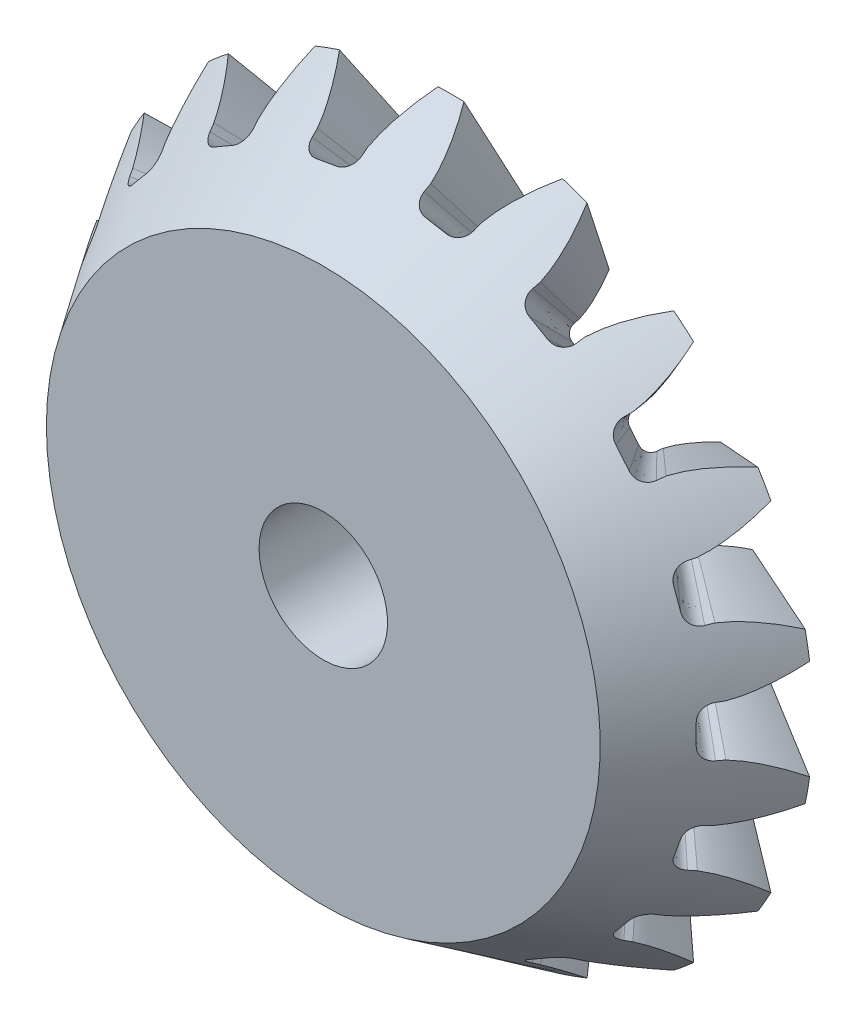
SolidWorks part; units mm, degrees
ref_plane "Front Plane" through (0, 0, 0) normal (0, 0, 1) x (1, 0, 0)
ref_plane "Top Plane" through (0, 0, 0) normal (0, 1, 0) x (1, 0, 0)
ref_plane "Right Plane" through (0, 0, 0) normal (1, 0, 0) x (0, 0, -1)
ref_axis "Gear Axis" through (0, 0, -1.3521) along (0, 0, 1)
sketch "Blank Sketch" plane through (0, 0, 0) normal (0, 1, 0) x (1, 0, 0)
  line L0 (0, 0) -> (0, -27.0416) construction
  line L1 (0, 0) -> (22.5, -15) construction
  line L2 (0, 0) -> (15.0115, -10.0077) construction
  line L3 (11.176, -15.7611) -> (15.6135, -9.1047)
  line L4 (15.6135, -9.1047) -> (23.5324, -13.4515)
  line L5 (23.5324, -13.4515) -> (17.9981, -21.7528)
  line L6 (17.9981, -21.7528) -> (4.175, -21.7528)
  line L7 (4.175, -21.7528) -> (4.175, -15.7611)
  line L8 (4.175, -15.7611) -> (11.176, -15.7611)
  line L9 (22.5, -15) -> (23.5324, -13.4515) construction
  line L10 (22.5, -15) -> (17.9981, -21.7528) construction
  line L11 (15.0115, -10.0077) -> (11.176, -15.7611) construction
  dimension "Axis" = 27.0416
  dimension "Cone" = 56.31
  dimension "Heel" = 27.0416
  dimension "Toe Cone" = 56.31
  dimension "Toe" = 18.0416
  dimension "Heel Square" = 90
  dimension "Addendum" = 1.8611
  dimension "Root Square" = 90
  dimension "Heel Rim" = 8.1158
  dimension "Toe Square" = 90
  dimension "Toe Rim" = 6.9147
  dimension "Front Square" = 90
  dimension "Face" = 4.927
  dimension "Back" = 13.8231
  dimension "Front" = 7.001
revolve "Blank" add sketch "Blank Sketch" angle 360 about L0
sketch "Cone Sketch" plane through (0, 0, 0) normal (0, 1, 0) x (1, 0, 0)
  line L0 (0, 0) -> (0, -27.0416) construction
  line L1 (0, 0) -> (24.5801, -16.3868)
  line L2 (0, 0) -> (12.9314, -8.6209)
  dimension "Axis" = 27.0416
  dimension "Toe Cone" = 56.31
  dimension "Heel Cone" = 56.31
  dimension "Heel" = 29.5416
  dimension "Toe" = 15.5416
ref_plane "Heel Plane" through (24.5801, 0, 16.3868) normal (0.8321, 0, 0.5547) x (0.5547, 0, -0.8321)
ref_plane "Toe Plane" through (12.9314, 0, 8.6209) normal (0.8321, 0, 0.5547) x (0.5547, 0, -0.8321)
sketch "Heel Section Sketch" plane through (24.5801, 0, 16.3868) normal (0.8321, 0, 0.5547) x (0.5547, 0, -0.8321)
  line L0 (0, 0) -> (-44.3125, 0) construction
  line L1 (-2.4254, 1.822) -> (-2.9568, 1.7989)
  line L2 (-2.4254, -1.822) -> (-2.9568, -1.7989)
  line L3 (4.4731, 5.3382) -> (4.4731, -5.3382)
  arc A0 (-2.9568, 1.7989) -> (-3.9494, 0.7429) centre (-2.9117, 0.762) ccw
  arc A1 (-3.9494, -0.7429) -> (-2.9568, -1.7989) centre (-2.9117, -0.762) ccw
  arc A2 (-3.9494, -0.7429) -> (-3.9494, 0.7429) centre (-44.3125, 0) ccw
  spline S0 degree 4 poles (-2.6185, 1.7952) (-2.5735, 1.8001) (-2.4634, 1.8153) (-2.3826, 1.8283) (-2.1666, 1.8686) (-2.0036, 1.9057) (-1.7812, 1.9593) (-1.5664, 2.0195) (-1.329, 2.0902) (-1.1027, 2.1645) (-0.8722, 2.2444) (-0.6468, 2.3281) (-0.412, 2.4198) (-0.1247, 2.538) (0.217, 2.6881) (0.607, 2.871) (1.0408, 3.0905) (1.4634, 3.3174) (1.8882, 3.5612) (2.2942, 3.8046) (2.7157, 4.0742) (3.0965, 4.325) (3.5292, 4.6295) (3.8609, 4.867) (4.3217, 5.2186) (4.5362, 5.3868) (4.8006, 5.5995) (4.951, 5.7231) (5.0219, 5.782) (5.0608, 5.8144) (5.0806, 5.831) knots 0 0 0 0 0 0.022117 0.039787 0.058126 0.081614 0.109122 0.13663 0.164138 0.191645 0.219153 0.246661 0.274169 0.305931 0.360947 0.415962 0.470978 0.525993 0.581009 0.636024 0.69104 0.746055 0.801071 0.856086 0.911102 0.955551 0.977775 0.988888 1 1 1 1 1 construction
  spline S1 degree 4 poles (-2.4254, 1.822) (-2.3913, 1.8275) (-2.324, 1.8392) (-2.1666, 1.8686) (-2.0036, 1.9057) (-1.7812, 1.9593) (-1.5664, 2.0195) (-1.329, 2.0902) (-1.1027, 2.1645) (-0.8722, 2.2444) (-0.6468, 2.3281) (-0.412, 2.4198) (-0.1247, 2.538) (0.217, 2.6881) (0.607, 2.871) (1.0408, 3.0905) (1.4634, 3.3174) (1.8882, 3.5612) (2.2942, 3.8046) (2.7157, 4.0742) (3.0965, 4.325) (3.5292, 4.6295) (3.8609, 4.867) (4.2239, 5.144) (4.3887, 5.2717) (4.4731, 5.3382) knots 0.022117 0.022117 0.022117 0.022117 0.022117 0.039787 0.058126 0.081614 0.109122 0.13663 0.164138 0.191645 0.219153 0.246661 0.274169 0.305931 0.360947 0.415962 0.470978 0.525993 0.581009 0.636024 0.69104 0.746055 0.801071 0.856086 0.911102 0.911102 0.911102 0.911102 0.911102
  spline S2 degree 4 poles (-2.6185, -1.7952) (-2.5735, -1.8001) (-2.4634, -1.8153) (-2.3826, -1.8283) (-2.1666, -1.8686) (-2.0036, -1.9057) (-1.7812, -1.9593) (-1.5664, -2.0195) (-1.329, -2.0902) (-1.1027, -2.1645) (-0.8722, -2.2444) (-0.6468, -2.3281) (-0.412, -2.4198) (-0.1247, -2.538) (0.217, -2.6881) (0.607, -2.871) (1.0408, -3.0905) (1.4634, -3.3174) (1.8882, -3.5612) (2.2942, -3.8046) (2.7157, -4.0742) (3.0965, -4.325) (3.5292, -4.6295) (3.8609, -4.867) (4.3217, -5.2186) (4.5362, -5.3868) (4.8006, -5.5995) (4.951, -5.7231) (5.0219, -5.782) (5.0608, -5.8144) (5.0806, -5.831) knots 0 0 0 0 0 0.022117 0.039787 0.058126 0.081614 0.109122 0.13663 0.164138 0.191645 0.219153 0.246661 0.274169 0.305931 0.360947 0.415962 0.470978 0.525993 0.581009 0.636024 0.69104 0.746055 0.801071 0.856086 0.911102 0.955551 0.977775 0.988888 1 1 1 1 1 construction
  spline S3 degree 4 poles (-2.4254, -1.822) (-2.3913, -1.8275) (-2.324, -1.8392) (-2.1666, -1.8686) (-2.0036, -1.9057) (-1.7812, -1.9593) (-1.5664, -2.0195) (-1.329, -2.0902) (-1.1027, -2.1645) (-0.8722, -2.2444) (-0.6468, -2.3281) (-0.412, -2.4198) (-0.1247, -2.538) (0.217, -2.6881) (0.607, -2.871) (1.0408, -3.0905) (1.4634, -3.3174) (1.8882, -3.5612) (2.2942, -3.8046) (2.7157, -4.0742) (3.0965, -4.325) (3.5292, -4.6295) (3.8609, -4.867) (4.2239, -5.144) (4.3887, -5.2717) (4.4731, -5.3382) knots 0.022117 0.022117 0.022117 0.022117 0.022117 0.039787 0.058126 0.081614 0.109122 0.13663 0.164138 0.191645 0.219153 0.246661 0.274169 0.305931 0.360947 0.415962 0.470978 0.525993 0.581009 0.636024 0.69104 0.746055 0.801071 0.856086 0.911102 0.911102 0.911102 0.911102 0.911102
  dimension "Root" = 40.3699
  dimension "Fillet" = 1.0378
  dimension "Centre" = 44.3125
sketch "Toe Section Sketch" plane through (12.9314, 0, 8.6209) normal (0.8321, 0, 0.5547) x (0.5547, 0, -0.8321)
  line L0 (0, 0) -> (-23.3125, 0) construction
  line L1 (-1.276, 0.9585) -> (-1.5556, 0.9464)
  line L2 (-1.276, -0.9585) -> (-1.5556, -0.9464)
  line L3 (2.3533, 2.8084) -> (2.3533, -2.8084)
  arc A0 (-1.5556, 0.9464) -> (-2.0777, 0.3908) centre (-1.5318, 0.4009) ccw
  arc A1 (-2.0777, -0.3908) -> (-1.5556, -0.9464) centre (-1.5318, -0.4009) ccw
  arc A2 (-2.0777, -0.3908) -> (-2.0777, 0.3908) centre (-23.3125, 0) ccw
  spline S0 degree 4 poles (-1.3801, 0.944) (-1.3498, 0.9477) (-1.2981, 0.9547) (-1.2515, 0.9622) (-1.1417, 0.9827) (-1.0525, 1.0029) (-0.9382, 1.0306) (-0.8233, 1.0626) (-0.6997, 1.0996) (-0.5798, 1.1388) (-0.459, 1.1807) (-0.3402, 1.2248) (-0.2168, 1.273) (-0.0656, 1.3353) (0.1141, 1.4142) (0.3193, 1.5104) (0.5475, 1.6259) (0.7699, 1.7453) (0.9934, 1.8735) (1.207, 2.0016) (1.4287, 2.1434) (1.6291, 2.2754) (1.8566, 2.4355) (2.0313, 2.5606) (2.2734, 2.7453) (2.4008, 2.8452) (2.5617, 2.975) (2.632, 3.0335) (2.6721, 3.067) knots 0 0 0 0 0 0.022117 0.039787 0.058126 0.081614 0.109122 0.13663 0.164138 0.191645 0.219153 0.246661 0.274169 0.305931 0.360947 0.415962 0.470978 0.525993 0.581009 0.636024 0.69104 0.746055 0.801071 0.856086 0.911102 0.955551 1 1 1 1 1 construction
  spline S1 degree 4 poles (-1.276, 0.9585) (-1.2581, 0.9614) (-1.2218, 0.9678) (-1.1417, 0.9827) (-1.0525, 1.0029) (-0.9382, 1.0306) (-0.8233, 1.0626) (-0.6997, 1.0996) (-0.5798, 1.1388) (-0.459, 1.1807) (-0.3402, 1.2248) (-0.2168, 1.273) (-0.0656, 1.3353) (0.1141, 1.4142) (0.3193, 1.5104) (0.5475, 1.6259) (0.7699, 1.7453) (0.9934, 1.8735) (1.207, 2.0016) (1.4287, 2.1434) (1.6291, 2.2754) (1.8566, 2.4355) (2.0313, 2.5606) (2.2221, 2.7061) (2.3088, 2.7734) (2.3533, 2.8084) knots 0.022117 0.022117 0.022117 0.022117 0.022117 0.039787 0.058126 0.081614 0.109122 0.13663 0.164138 0.191645 0.219153 0.246661 0.274169 0.305931 0.360947 0.415962 0.470978 0.525993 0.581009 0.636024 0.69104 0.746055 0.801071 0.856086 0.911102 0.911102 0.911102 0.911102 0.911102
  spline S2 degree 4 poles (-1.3801, -0.944) (-1.3498, -0.9477) (-1.2981, -0.9547) (-1.2515, -0.9622) (-1.1417, -0.9827) (-1.0525, -1.0029) (-0.9382, -1.0306) (-0.8233, -1.0626) (-0.6997, -1.0996) (-0.5798, -1.1388) (-0.459, -1.1807) (-0.3402, -1.2248) (-0.2168, -1.273) (-0.0656, -1.3353) (0.1141, -1.4142) (0.3193, -1.5104) (0.5475, -1.6259) (0.7699, -1.7453) (0.9934, -1.8735) (1.207, -2.0016) (1.4287, -2.1434) (1.6291, -2.2754) (1.8566, -2.4355) (2.0313, -2.5606) (2.2734, -2.7453) (2.4008, -2.8452) (2.5617, -2.975) (2.632, -3.0335) (2.6721, -3.067) knots 0 0 0 0 0 0.022117 0.039787 0.058126 0.081614 0.109122 0.13663 0.164138 0.191645 0.219153 0.246661 0.274169 0.305931 0.360947 0.415962 0.470978 0.525993 0.581009 0.636024 0.69104 0.746055 0.801071 0.856086 0.911102 0.955551 1 1 1 1 1 construction
  spline S3 degree 4 poles (-1.276, -0.9585) (-1.2581, -0.9614) (-1.2218, -0.9678) (-1.1417, -0.9827) (-1.0525, -1.0029) (-0.9382, -1.0306) (-0.8233, -1.0626) (-0.6997, -1.0996) (-0.5798, -1.1388) (-0.459, -1.1807) (-0.3402, -1.2248) (-0.2168, -1.273) (-0.0656, -1.3353) (0.1141, -1.4142) (0.3193, -1.5104) (0.5475, -1.6259) (0.7699, -1.7453) (0.9934, -1.8735) (1.207, -2.0016) (1.4287, -2.1434) (1.6291, -2.2754) (1.8566, -2.4355) (2.0313, -2.5606) (2.2221, -2.7061) (2.3088, -2.7734) (2.3533, -2.8084) knots 0.022117 0.022117 0.022117 0.022117 0.022117 0.039787 0.058126 0.081614 0.109122 0.13663 0.164138 0.191645 0.219153 0.246661 0.274169 0.305931 0.360947 0.415962 0.470978 0.525993 0.581009 0.636024 0.69104 0.746055 0.801071 0.856086 0.911102 0.911102 0.911102 0.911102 0.911102
  dimension "Root" = 21.2383
  dimension "Fillet" = 0.546
  dimension "Centre" = 23.3125
loft "Tooth Space" cut profiles "Heel Section Sketch", "Toe Section Sketch"
pattern_circular "Teeth" count 18 over 360 about axis through (0, 0, -1.3521) along (0, 0, 1) of "Tooth Space"
equation "\"No. of Teeth\"= 18"
equation "\"Module\"= 2.5"
equation "\"Bore Diameter\" = 8.35"
equation "\"Pressure Angle\"= 20"
equation "\"Shaft Angle\"= 90"
equation "\"Mate Teeth\"= 12"
equation "\"Pitch Cone Angle\"= IIF ( ( \"Mate Teeth\" / \"No. of Teeth\" + cos ( \"Shaft Angle\" ) ) > 0 , atn ( sin ( \"Shaft Angle\" ) / ( \"Mate Teeth\" / \"No. of Teeth\" + cos ( \"Shaft Angle\" ) ) ) , 180 + atn ( sin ( \"Shaft Angle\" ) / ( \"Mate Teeth\" / \"No. of Teeth\" + cos ( \"Shaft Angle\" ) ) ) )"
equation "\"Mate Cone Angle\"= \"Shaft Angle\" - \"Pitch Cone Angle\""
equation "\"Addendum\"= IIF ( \"No. of Teeth\" >= \"Mate Teeth\" , 0.54 * \"Module\" + 0.46 * \"Module\" / ( ( \"No. of Teeth\" * cos ( \"Mate Cone Angle\" ) ) / ( \"Mate Teeth\" * cos ( \"Pitch Cone Angle\" ) ) ) , 2 * \"Module\" - ( 0.54 * \"Module\" + 0.46 * \"Module\" / ( ( \"Mate Teeth\" * cos ( \"Pitch Cone Angle\" ) ) / ( \"No. of Teeth\" * cos ( \"Mate Cone Angle\" ) ) ) ) )"
equation "\"Outer Diameter\"= \"No. of Teeth\" * \"Module\" + 2 * \"Addendum\" * cos ( \"Pitch Cone Angle\" )"
equation "\"Pitch Diameter\"= \"No. of Teeth\" * \"Module\""
equation "\"Backlash\" = IIF ( \"Module\" <= 1 , 0.3 * \"Module\" , 0.3 )"
equation "\"Arc Length\"= ( ( \"Module\" * pi ) / 2 + \"Backlash\" - 2 * ( \"Addendum\" - \"Module\" ) * tan ( \"Pressure Angle\" ) )"
equation "\"Fillet Radius\"= 0.38 * \"Module\""
equation "\"Mate Addendum\"= 2 * \"Module\" - \"Addendum\""
equation "\"Dedendum\"= 2.188 * \"Module\" - \"Addendum\""
equation "\"Tooth Depth\"= \"Addendum\" + \"Dedendum\""
equation "\"Mate Dedendum\"= 2.188 * \"Module\" - \"Mate Addendum\""
equation "\"Face Width\"= 9"
equation "\"Cone Distance\"= \"Pitch Diameter\" / ( 2 * sin ( \"Pitch Cone Angle\" ) )"
equation "\"Dedendum Angle\"= atn ( \"Dedendum\" / \"Cone Distance\" )"
equation "\"Mate Dedendum Angle\"= atn ( \"Mate Dedendum\" / \"Cone Distance\" )"
equation "\"Face Angle\"= \"Pitch Cone Angle\" + \"Mate Dedendum Angle\""
equation "\"Root Angle\"= \"Pitch Cone Angle\" - \"Dedendum Angle\""
equation "\"Overrun\"= \"Module\""
equation "\"Back Cone Pitch Diameter\"= \"Pitch Diameter\" / cos ( \"Pitch Cone Angle\" )"
equation "\"Back Cone Outer Diameter\"= \"Back Cone Pitch Diameter\" + 2 * \"Addendum\""
equation "\"Root Diameter\"= \"Back Cone Outer Diameter\" - 2 * \"Tooth Depth\""
equation "\"Base Diameter\"= \"Back Cone Pitch Diameter\" * cos ( \"Pressure Angle\" )"
equation "\"Base Radius\"= \"Base Diameter\" / 2"
equation "\"Tooth Thickness\"= \"Module\" * pi - \"Arc Length\""
equation "\"Half Space Angle\"= ( \"Arc Length\" / \"Back Cone Pitch Diameter\" ) * 180 / pi"
equation "\"Involute Fn\"= tan ( \"Pressure Angle\" ) - \"Pressure Angle\" * pi / 180"
equation "\"Flank Offset\"= \"Arc Length\" / \"Back Cone Pitch Diameter\" - \"Involute Fn\""
equation "\"Tip Cap Diameter\"= \"Back Cone Outer Diameter\" + 2 * \"Module\""
equation "\"Flank Start Diameter\"= IIF ( \"Base Diameter\" >= ( \"Root Diameter\" + 3 * \"Fillet Radius\" ) , \"Base Diameter\" , \"Root Diameter\" + 3 * \"Fillet Radius\" )"
equation "\"Involute t1\"= ( abs ( ( \"Flank Start Diameter\" / \"Base Diameter\" ) ^ 2 - 1 ) ) ^ 0.5"
equation "\"Involute t2\"= ( abs ( ( \"Tip Cap Diameter\" / \"Base Diameter\" ) ^ 2 - 1 ) ) ^ 0.5"
equation "\"Flank Arc Radius\"= ( \"Back Cone Pitch Diameter\" / 2 ) * sin ( \"Pressure Angle\" )"
equation "\"Flank Centre Angle\"= \"Half Space Angle\" + \"Pressure Angle\""
equation "\"Heel Distance\"= \"Cone Distance\" + \"Overrun\""
equation "\"Toe Distance\"= \"Cone Distance\" - \"Face Width\" - \"Overrun\""
equation "\"Heel Scale\"= \"Heel Distance\" / \"Cone Distance\""
equation "\"Toe Scale\"= \"Toe Distance\" / \"Cone Distance\""
equation "\"Heel Virtual Radius\"= \"Heel Distance\" * tan ( \"Pitch Cone Angle\" )"
equation "\"Toe Virtual Radius\"= \"Toe Distance\" * tan ( \"Pitch Cone Angle\" )"
equation "\"Axis@Blank Sketch\"= \"Cone Distance\""
equation "\"Cone@Blank Sketch\"= \"Pitch Cone Angle\""
equation "\"Heel@Blank Sketch\"= \"Cone Distance\""
equation "\"Toe Cone@Blank Sketch\"= \"Pitch Cone Angle\""
equation "\"Toe@Blank Sketch\"= \"Cone Distance\" - \"Face Width\""
equation "\"Addendum@Blank Sketch\"= \"Addendum\""
equation "\"Heel Rim@Blank Sketch\"= \"Dedendum\" + \"Module\" / cos ( \"Pitch Cone Angle\" )"
equation "\"Toe Rim@Blank Sketch\"= \"Dedendum\" - \"Face Width\" * tan ( \"Dedendum Angle\" ) + \"Module\" / cos ( \"Pitch Cone Angle\" )"
equation "\"Face@Blank Sketch\"= \"Mate Dedendum Angle\""
equation "\"Back@Blank Sketch\"= \"Cone Distance\" * sin ( \"Pitch Cone Angle\" ) - \"Dedendum\" * cos ( \"Pitch Cone Angle\" ) - \"Module\" - \"Bore Diameter\" / 2"
equation "\"Front@Blank Sketch\"= ( \"Cone Distance\" - \"Face Width\" ) * sin ( \"Pitch Cone Angle\" ) - ( \"Dedendum\" - \"Face Width\" * tan ( \"Dedendum Angle\" ) + \"Module\" / cos ( \"Pitch Cone Angle\" ) ) * cos ( \"Pitch Cone Angle\" ) - \"Bore Diameter\" / 2"
equation "\"Axis@Cone Sketch\"= \"Cone Distance\""
equation "\"Heel Cone@Cone Sketch\"= \"Pitch Cone Angle\""
equation "\"Heel@Cone Sketch\"= \"Heel Distance\""
equation "\"Toe Cone@Cone Sketch\"= \"Pitch Cone Angle\""
equation "\"Toe@Cone Sketch\"= \"Toe Distance\""
equation "\"Centre@Heel Section Sketch\"= \"Heel Virtual Radius\""
equation "\"Root@Heel Section Sketch\"= ( \"Root Diameter\" / 2 ) * \"Heel Scale\""
equation "\"Fillet@Heel Section Sketch\"= ( \"Fillet Radius\" ) * \"Heel Scale\""
equation "\"Centre@Toe Section Sketch\"= \"Toe Virtual Radius\""
equation "\"Root@Toe Section Sketch\"= ( \"Root Diameter\" / 2 ) * \"Toe Scale\""
equation "\"Fillet@Toe Section Sketch\"= ( \"Fillet Radius\" ) * \"Toe Scale\""
equation "\"Count@Teeth\"= \"No. of Teeth\""
